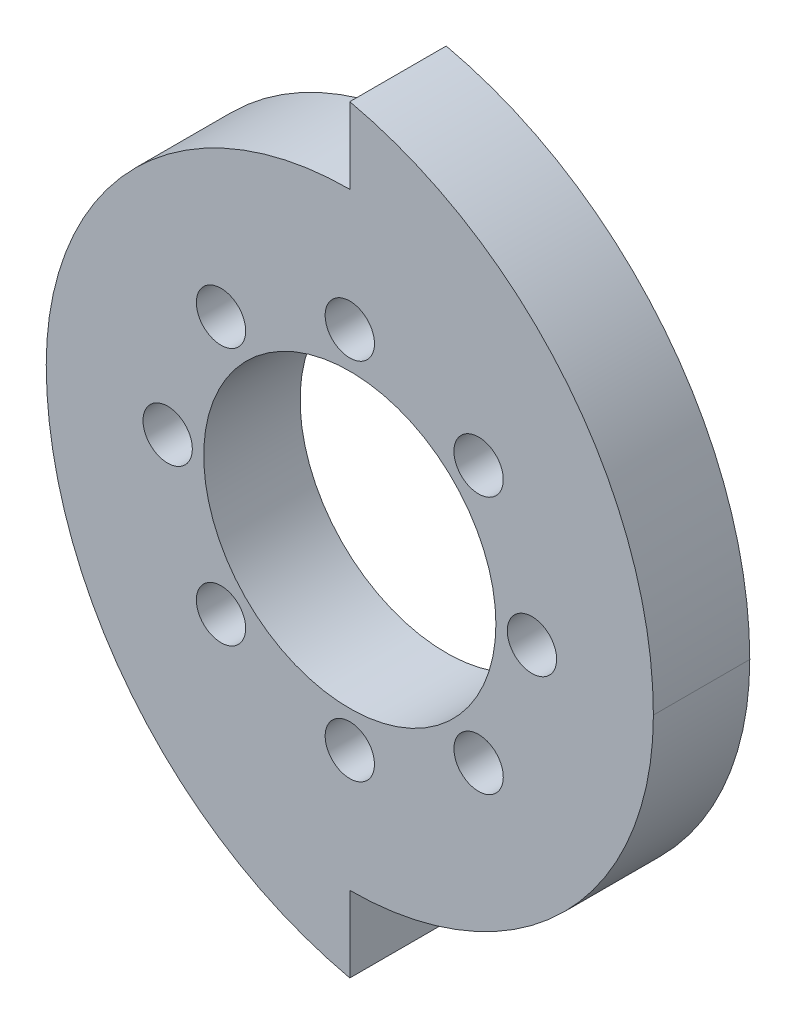
SolidWorks part; units mm, degrees
material "AISI 316 Stainless Steel Sheet (SS)"
ref_plane "Front Plane" through (0, 0, 0) normal (0, 0, 1) x (1, 0, 0)
ref_plane "Top Plane" through (0, 0, 0) normal (0, 1, 0) x (1, 0, 0)
ref_plane "Right Plane" through (0, 0, 0) normal (1, 0, 0) x (0, 0, -1)
sketch "Sketch3" plane through (0, 0, 0) normal (0, 0, 1) x (1, 0, 0)
  line L5 (0, 20) -> (0, 25)
  line L12 (0, -20) -> (0, -25)
  arc A9 (0, 25) -> (-20, 0) centre (5.625, 0) ccw construction
  arc A11 (0, -25) -> (20, 0) centre (-5.625, 0) ccw construction
  arc A14 (0, 25) -> (20, 0) centre (-5.625, 0) cw
  arc A15 (0, -25) -> (-20, 0) centre (5.625, 0) cw
  arc A16 (0, 20) -> (-20, 0) centre (0, 0) ccw
  arc A17 (20, 0) -> (0, -20) centre (0, 0) cw
  dimension "D2" = 5
  dimension "D1" = 40
extrude "Boss-Extrude1" add sketch "Sketch3" along normal blind 6.35
sketch "Sketch4" plane through (0, 0, 6.35) normal (0, 0, 1) x (1, 0, 0)
  circle A10 centre (0, 0) radius 9.625
  circle A11 centre (0, 12) radius 1.625
  dimension "D2" = 12
  dimension "D3" = 19.25
  dimension "D1" = 3.25
extrude "Cut-Extrude1" cut sketch "Sketch4" against normal through all
ref_axis "Axis1" through (0, 0, -0.475) along (0, 0, 1)
pattern_circular "CirPattern1" count 8 over 360 about axis through (0, 0, -0.475) along (0, 0, 1) of "Cut-Extrude1"
